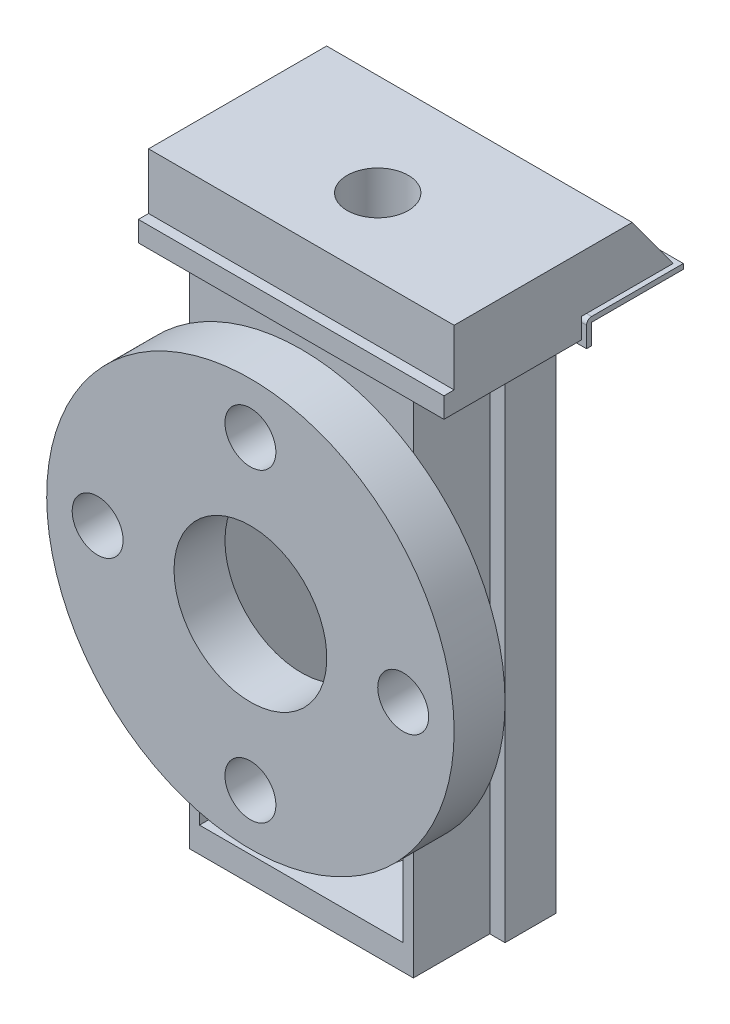
SolidWorks part; units mm, degrees
material "1060 合金"
ref_plane "前视基准面" through (0, 0, 0) normal (0, 0, 1) x (1, 0, 0)
ref_plane "上视基准面" through (0, 0, 0) normal (0, 1, 0) x (1, 0, 0)
ref_plane "右视基准面" through (0, 0, 0) normal (1, 0, 0) x (0, 0, -1)
sketch "草图1" plane through (0, 0, 0) normal (0, 0, 1) x (1, 0, 0)
  line L0 (0, -50) -> (0, 50)
  line L1 (-25, 50) -> (25, 50)
  line L2 (-25, 50) -> (-25, -50)
  line L3 (-25, -50) -> (25, -50)
  line L4 (25, 50) -> (25, -50)
  line L5 (-25, 0) -> (25, 0)
  line L6 (-20, 45) -> (20, 45)
  line L7 (-20, 0) -> (0, 0)
  line L8 (-20, 45) -> (-20, -45)
  line L9 (-20, -45) -> (20, -45)
  line L10 (0, 45) -> (0, -45)
  line L11 (20, 45) -> (20, -45)
  point P8 (0, 0)
  dimension "D1" = 50
  dimension "D2" = 100
  dimension "D3" = 45
  dimension "D4" = 20
extrude "凸台-拉伸1" add sketch "草图1" along normal blind 25 contours L6 L11 L5 L4 L1 L0 | L8 L6 L0 L1 L2 L5 | L9 L8 L5 L2 L3 L0 | L5 L11 L9 L0 L3 L4 region at (-12.5, -49.441, 0) region at (0.559, -47.5, 0) region at (-24.441, 25, 0) region at (22.5, 0.559, 0)
sketch "草图2" plane through (0, 0, 0) normal (0, 1, 0) x (1, 0, 0)
  line L0 (0, -26.5538) -> (0, 0.2015)
  line L1 (25, -25) -> (22, -25)
  line L6 (22, -25) -> (22, -10)
  line L7 (25, -25) -> (25, -10)
  line L8 (-25, -25) -> (-22, -25)
  line L9 (-25, -25) -> (-25, -10)
  line L10 (-25, -10) -> (-22, -10)
  line L11 (-22, -25) -> (-22, -10)
  line L12 (25, -10) -> (22, -10)
  dimension "D1" = 15
  dimension "D2" = 3
sketch "草图4" plane through (0, 0, 0) normal (0, 1, 0) x (1, 0, 0)
extrude "切除-拉伸1" cut sketch "草图2" against normal blind 100 and the other way blind 100 contours L10 L11 L8 L9 | L7 L12 L6 L1
ref_plane "基准面1" through (0, 50, 0) normal (0, 1, 0) x (1, 0, 0)
sketch "草图5" plane through (0, 50, 0) normal (0, 1, 0) x (1, 0, 0)
  line L0 (0, 1.2946) -> (0, -26.2238)
  line L1 (30, -27) -> (30, 18)
  line L2 (30, -27) -> (-30, -27)
  line L3 (0, -27) -> (0, 18)
  line L4 (30, 18) -> (-30, 18)
  line L5 (-30, -27) -> (-30, 18)
  line L6 (-20.7189, 0) -> (-20.7189, 18)
  line L7 (-25, 0) -> (25, 0) construction
  dimension "D1" = 45
  dimension "D2" = 60
extrude "凸台-拉伸2" add sketch "草图5" along normal blind 15 contours L1 L4 L3 L0 L2 | L5 L2 L3 L0 L4 region at (15, 50, 4.5) region at (-15, 50, 4.5)
ref_plane "基准面2" through (-30, 0, 0) normal (-1, 0, 0) x (0, 0, 1)
sketch "草图7" plane through (-30, 0, 0) normal (-1, 0, 0) x (0, 0, 1)
  line L0 (25, 50) -> (25, 65)
  line L1 (27, 65) -> (-18, 65) construction
  line L2 (25, 65) -> (27, 65)
  line L3 (27, 65) -> (27, 54)
  line L4 (27, 65) -> (27, 50) construction
  line L5 (27, 54) -> (25, 54)
  line M3 (27, 50) -> (27, 65)
  line M4 (27, 65) -> (-18, 65)
  dimension "D1" = 4
extrude "切除-拉伸2" cut sketch "草图7" against normal blind 103 contours L5 L0 M3 M4 region at (-30, 59.5, 26)
sketch "草图12" plane through (-30, 0, 0) normal (-1, 0, 0) x (0, 0, 1)
  line L0 (25, 54) -> (-18, 54)
  line L1 (-18, 65) -> (-18, 50) construction
  line L2 (-18, 65) -> (-18, 54)
  line L3 (-18, 65) -> (-9.9689, 65)
  line L4 (25, 65) -> (-18, 65) construction
  line L5 (-9.9689, 65) -> (-18, 54)
extrude "切除-拉伸3" cut sketch "草图12" against normal blind 103 contours L5 L3 L2 region at (-30, 61.3333, -15.323)
sketch "草图13" plane through (-30, 0, 0) normal (-1, 0, 0) x (0, 0, 1)
  line L0 (25, 54) -> (-18, 54)
  line L1 (0, 50) -> (0, 54)
  line L2 (0, 54) -> (-18, 54)
  line L4 (0, 54) -> (-18, 54)
  line L5 (0, 54) -> (0, 49.192)
  line L6 (0, 49.192) -> (-18, 49.192)
  line L7 (-18, 54) -> (-18, 49.192)
extrude "切除-拉伸4" cut sketch "草图13" against normal blind 103 contours L0 L7 L6 L5 L1 region at (-30, 51.596, -9)
ref_plane "基准面3" through (-31, 0, 0) normal (-1, 0, 0) x (0, 0, 1)
sketch "草图14" plane through (-31, 0, 0) normal (-1, 0, 0) x (0, 0, 1)
  line L0 (0, 49) -> (0, 54)
  line L1 (0, 50) -> (0, -50) construction
  line L2 (0, 54) -> (-19, 54)
  line L3 (-19, 54) -> (-19, 53)
  line L4 (-19, 53) -> (-1, 53)
  line L5 (-1, 53) -> (-1, 49)
  line L6 (-1, 49) -> (0, 49)
  circle A0 centre (-1, 53) radius 1
  dimension "D1" = 1
  dimension "D2" = 1
  dimension "D3" = 19
extrude "凸台-拉伸4" add sketch "草图14" against normal blind 62 contours A0 L2 L3 L4 | A0 L4 L5 | A0 L5 L6 L0 region at (-31, 50.615, -0.4815) region at (-31, 53.1415, -0.8585) region at (-31, 53.5034, -10.3913)
sketch "草图15" plane through (0, 50, 0) normal (0, 1, 0) x (1, 0, 0)
  line L0 (-22, -10) -> (22, -10)
  circle A0 centre (0, -10) radius 6
extrude "切除-拉伸5" cut sketch "草图15" against normal blind 123 and the other way blind 30 contours A0
sketch "草图16" plane through (0, 53, 0) normal (0, -1, 0) x (1, 0, 0)
  line L0 (0, -1) -> (0, -19)
  line L1 (31, -1) -> (-31, -1) construction
  line L2 (31, -19) -> (-31, -19) construction
  line L3 (0, -10) -> (31, -10)
  line L4 (31, -19) -> (31, -1) construction
  line L5 (0, -10) -> (-31, -10)
  line L6 (-31, -19) -> (-31, -1) construction
  line L7 (-15, -10) -> (0, -10)
  line L8 (15, -10) -> (0, -10)
  circle A0 centre (-15, -10) radius 3
  circle A1 centre (15, -10) radius 3
extrude "切除-拉伸6" cut sketch "草图16" against normal blind 4 contours A1 L3 | A1 L3 | L5 A0 | L5 A0 region at (15, 53, -8.7268) region at (15, 53, -11.2732) region at (-15, 53, -11.2732) region at (-15, 53, -8.7268)
ref_plane "基准面6" through (-30, 54, -1) normal (0, 0, -1) x (-1, 0, 0)
ref_plane "基准面9" through (0, 0, 25) normal (0, 0, 1) x (1, 0, 0)
sketch "草图18" plane through (0, 0, 25) normal (0, 0, 1) x (1, 0, 0)
  line L0 (-20, 45) -> (-20, -45) construction
  line L1 (20, 45) -> (-20, 45)
  line L2 (20, 45) -> (20, 30.3709)
  line L3 (20, 30.3709) -> (-20, 30.3709)
  line L4 (-20, 45) -> (-20, 30.3709)
extrude "凸台-拉伸5" add sketch "草图18" against normal blind 5
sketch "草图19" plane through (0, 0, 25) normal (0, 0, 1) x (1, 0, 0)
  line L0 (0, 54) -> (0, 0)
  line L1 (30, 54) -> (-30, 54) construction
  circle A1 centre (0, 5.9162) radius 40
  circle A2 centre (0, 5.9162) radius 30
  circle A3 centre (0, 5.9162) radius 10
  circle A4 centre (0, 5.9162) radius 15
  circle A5 centre (0, 35.9162) radius 5
  circle A6 centre (30, 5.9162) radius 5
  circle A7 centre (0, -24.0838) radius 5
  circle A8 centre (-30, 5.9162) radius 5
  point P21 (0, 5.9162)
  dimension "D1" = 80
  dimension "D2" = 4
extrude "凸台-拉伸7" add sketch "草图19" along normal blind 10 contours A3 | A4 A3 | A4 A2 | A2 A1 region at (27.4843, 33.4005, 25) region at (6.8711, 12.7873, 25) region at (10.3066, 16.2228, 25) region at (-3.9515, 31.6205, 25)
extrude "切除-拉伸8" cut sketch "草图19<8>" along normal blind 25 contours A4
sketch "草图19<8>" plane through (0, 0, 25) normal (0, 0, 1) x (1, 0, 0) same geometry as "草图19"
